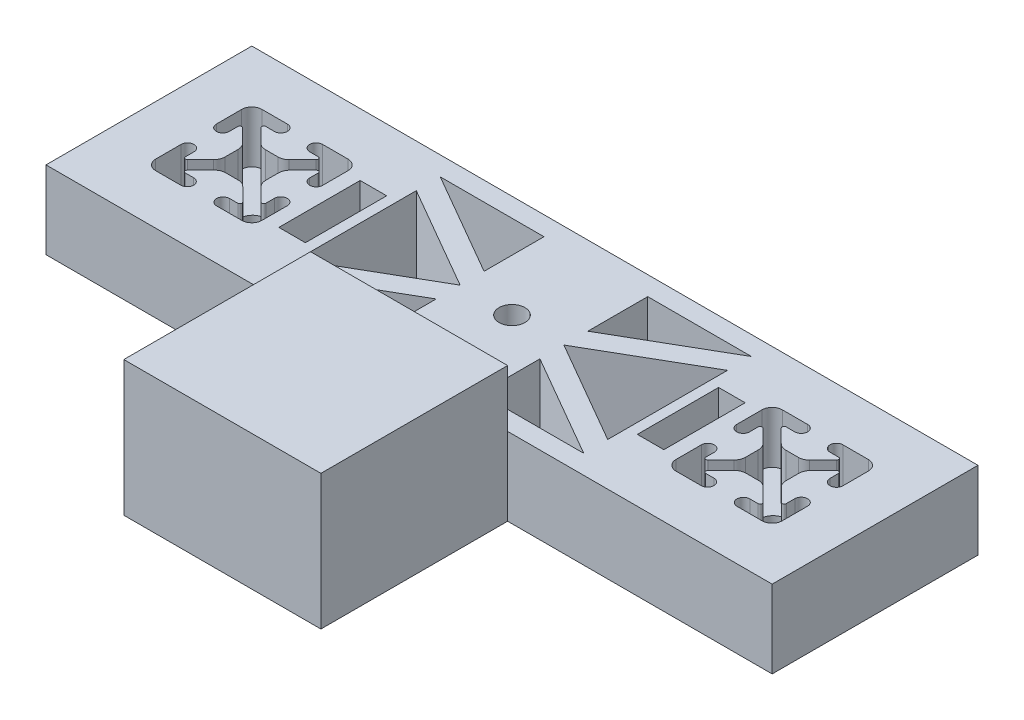
SolidWorks part; units mm, degrees
ref_plane "Front" through (0, 0, 0) normal (0, 0, 1) x (1, 0, 0)
ref_plane "Top" through (0, 0, 0) normal (0, 1, 0) x (1, 0, 0)
ref_plane "Right" through (0, 0, 0) normal (1, 0, 0) x (0, 0, -1)
sketch "Sketch1" plane through (0, 0, 0) normal (0, 1, 0) x (1, 0, 0)
  line L1 (0, 0) -> (177.8, 0)
  line L2 (0, 0) -> (0, 50.4)
  line L3 (0, 50.4) -> (177.8, 50.4)
  line L4 (177.8, 0) -> (177.8, 50.4)
  dimension "D1" = 177.8
  dimension "D2" = 50.4
extrude "Boss-Extrude1" add sketch "Sketch1" along normal blind 6.35
sketch "Sketch2" plane through (0, 6.35, 0) normal (0, 1, 0) x (1, 0, 0)
  line L0 (37.6996, 29.52) -> (37.6996, 35.7372) construction
  line L1 (35.7368, 37.7) -> (29.5196, 37.7) construction
  line L2 (29.5196, 35.56) -> (31.619, 35.56) construction
  line L3 (32.3326, 33.8353) -> (28.9966, 30.504) construction
  line L4 (26.7566, 29.5771) -> (23.643, 29.5771) construction
  line L5 (21.403, 30.504) -> (18.067, 33.8353) construction
  line L6 (18.7806, 35.56) -> (20.88, 35.56) construction
  line L7 (20.88, 37.7) -> (14.6628, 37.7) construction
  line L8 (12.7, 35.7372) -> (12.7, 29.52) construction
  line L9 (14.84, 29.52) -> (14.84, 31.5965) construction
  line L10 (16.5637, 32.3112) -> (19.7659, 29.1135) construction
  line L11 (20.743, 26.7568) -> (20.743, 23.6432) construction
  line L12 (19.7659, 21.2865) -> (16.5637, 18.0888) construction
  line L13 (14.84, 18.8035) -> (14.84, 20.88) construction
  line L14 (12.7, 20.88) -> (12.7, 14.6628) construction
  line L15 (14.6628, 12.7) -> (20.8121, 12.7) construction
  line L16 (20.8121, 14.84) -> (18.7806, 14.84) construction
  line L17 (18.067, 16.5647) -> (21.403, 19.896) construction
  line L18 (23.643, 20.8229) -> (26.7566, 20.8229) construction
  line L19 (28.9966, 19.896) -> (32.3326, 16.5647) construction
  line L20 (31.619, 14.84) -> (29.5875, 14.84) construction
  line L21 (29.5875, 12.7) -> (35.7368, 12.7) construction
  line L22 (37.6996, 14.6628) -> (37.6996, 20.88) construction
  line L23 (35.5596, 20.88) -> (35.5596, 18.8035) construction
  line L24 (33.8359, 18.0888) -> (30.6337, 21.2865) construction
  line L25 (29.6566, 23.6432) -> (29.6566, 26.7568) construction
  line L26 (30.6337, 29.1135) -> (33.8359, 32.3112) construction
  line L27 (35.5596, 31.5965) -> (35.5596, 29.52) construction
  line L28 (0, 50.4) -> (0, 0) construction
  line L29 (177.8, 50.4) -> (0, 50.4) construction
  line L30 (0, 0) -> (177.8, 0) construction
  line L31 (88.9, 50.4) -> (88.9, 0) construction
  line L32 (142.2404, 31.5965) -> (142.2404, 29.52) construction
  line L33 (147.1663, 29.1135) -> (143.9641, 32.3112) construction
  line L34 (148.1434, 23.6432) -> (148.1434, 26.7568) construction
  line L35 (143.9641, 18.0888) -> (147.1663, 21.2865) construction
  line L36 (142.2404, 20.88) -> (142.2404, 18.8035) construction
  line L37 (140.1004, 14.6628) -> (140.1004, 20.88) construction
  line L38 (148.2125, 12.7) -> (142.0632, 12.7) construction
  line L39 (146.181, 14.84) -> (148.2125, 14.84) construction
  line L40 (148.8034, 19.896) -> (145.4674, 16.5647) construction
  line L41 (154.157, 20.8229) -> (151.0434, 20.8229) construction
  line L42 (159.733, 16.5647) -> (156.397, 19.896) construction
  line L43 (156.9879, 14.84) -> (159.0194, 14.84) construction
  line L44 (163.1372, 12.7) -> (156.9879, 12.7) construction
  line L45 (165.1, 20.88) -> (165.1, 14.6628) construction
  line L46 (162.96, 18.8035) -> (162.96, 20.88) construction
  line L47 (158.0341, 21.2865) -> (161.2363, 18.0888) construction
  line L48 (157.057, 26.7568) -> (157.057, 23.6432) construction
  line L49 (161.2363, 32.3112) -> (158.0341, 29.1135) construction
  line L50 (162.96, 29.52) -> (162.96, 31.5965) construction
  line L51 (165.1, 35.7372) -> (165.1, 29.52) construction
  line L52 (156.92, 37.7) -> (163.1372, 37.7) construction
  line L53 (159.0194, 35.56) -> (156.92, 35.56) construction
  line L54 (156.397, 30.504) -> (159.733, 33.8353) construction
  line L55 (151.0434, 29.5771) -> (154.157, 29.5771) construction
  line L56 (145.4674, 33.8353) -> (148.8034, 30.504) construction
  line L57 (148.2804, 35.56) -> (146.181, 35.56) construction
  line L58 (142.0632, 37.7) -> (148.2804, 37.7) construction
  line L59 (140.1004, 29.52) -> (140.1004, 35.7372) construction
  line L60 (38.2076, 29.52) -> (38.2076, 35.7372)
  line L62 (0, 50.4) -> (0, 0)
  line L63 (0, 0) -> (177.8, 0)
  line L64 (177.8, 50.4) -> (177.8, 0)
  line L65 (35.7368, 38.208) -> (29.5196, 38.208)
  line L66 (29.5196, 35.052) -> (31.619, 35.052)
  line L67 (31.9737, 34.1948) -> (28.6376, 30.8635)
  line L68 (26.7566, 30.0851) -> (23.643, 30.0851)
  line L69 (21.762, 30.8635) -> (18.4259, 34.1948)
  line L70 (18.7806, 35.052) -> (20.88, 35.052)
  line L71 (20.88, 38.208) -> (14.6628, 38.208)
  line L72 (12.192, 35.7372) -> (12.192, 29.52)
  line L73 (15.348, 29.52) -> (15.348, 31.5965)
  line L74 (16.2047, 31.9517) -> (19.4069, 28.7541)
  line L75 (20.235, 26.7568) -> (20.235, 23.6432)
  line L76 (19.4069, 21.6459) -> (16.2047, 18.4483)
  line L77 (15.348, 18.8035) -> (15.348, 20.88)
  line L78 (12.192, 20.88) -> (12.192, 14.6628)
  line L79 (14.6628, 12.192) -> (20.8121, 12.192)
  line L80 (20.8121, 15.348) -> (18.7806, 15.348)
  line L81 (18.4259, 16.2052) -> (21.762, 19.5365)
  line L82 (23.643, 20.3149) -> (26.7566, 20.3149)
  line L83 (28.6376, 19.5365) -> (31.9737, 16.2052)
  line L84 (31.619, 15.348) -> (29.5875, 15.348)
  line L85 (29.5875, 12.192) -> (35.7368, 12.192)
  line L86 (38.2076, 14.6628) -> (38.2076, 20.88)
  line L87 (35.0516, 20.88) -> (35.0516, 18.8035)
  line L88 (34.1949, 18.4483) -> (30.9927, 21.6459)
  line L89 (30.1646, 23.6432) -> (30.1646, 26.7568)
  line L90 (30.9927, 28.7541) -> (34.1949, 31.9517)
  line L91 (35.0516, 31.5965) -> (35.0516, 29.52)
  line L92 (142.7484, 31.5965) -> (142.7484, 29.52)
  line L93 (139.5924, 29.52) -> (139.5924, 35.7372)
  line L94 (142.0632, 38.208) -> (148.2804, 38.208)
  line L95 (148.2804, 35.052) -> (146.181, 35.052)
  line L96 (145.8263, 34.1948) -> (149.1624, 30.8635)
  line L97 (151.0434, 30.0851) -> (154.157, 30.0851)
  line L98 (156.038, 30.8635) -> (159.3741, 34.1948)
  line L99 (159.0194, 35.052) -> (156.92, 35.052)
  line L100 (156.92, 38.208) -> (163.1372, 38.208)
  line L101 (165.608, 35.7372) -> (165.608, 29.52)
  line L102 (162.452, 29.52) -> (162.452, 31.5965)
  line L103 (161.5953, 31.9517) -> (158.3931, 28.7541)
  line L104 (157.565, 26.7568) -> (157.565, 23.6432)
  line L105 (158.3931, 21.6459) -> (161.5953, 18.4483)
  line L106 (162.452, 18.8035) -> (162.452, 20.88)
  line L107 (165.608, 20.88) -> (165.608, 14.6628)
  line L108 (163.1372, 12.192) -> (156.9879, 12.192)
  line L109 (156.9879, 15.348) -> (159.0194, 15.348)
  line L110 (159.3741, 16.2052) -> (156.038, 19.5365)
  line L111 (154.157, 20.3149) -> (151.0434, 20.3149)
  line L112 (149.1624, 19.5365) -> (145.8263, 16.2052)
  line L113 (146.181, 15.348) -> (148.2125, 15.348)
  line L114 (148.2125, 12.192) -> (142.0632, 12.192)
  line L115 (139.5924, 14.6628) -> (139.5924, 20.88)
  line L116 (142.7484, 20.88) -> (142.7484, 18.8035)
  line L117 (143.6051, 18.4483) -> (146.8073, 21.6459)
  line L118 (147.6354, 23.6432) -> (147.6354, 26.7568)
  line L119 (146.8073, 28.7541) -> (143.6051, 31.9517)
  line L120 (177.8, 50.4) -> (0, 50.4)
  arc A1 (37.6996, 35.7372) -> (35.7368, 37.7) centre (35.7368, 35.7372) ccw construction
  arc A2 (29.5196, 37.7) -> (29.5196, 35.56) centre (29.5196, 36.63) ccw construction
  arc A3 (31.619, 35.56) -> (32.3326, 33.8353) centre (31.619, 34.55) cw construction
  arc A4 (28.9966, 30.504) -> (26.7566, 29.5771) centre (26.7566, 32.7471) cw construction
  arc A5 (23.643, 29.5771) -> (21.403, 30.504) centre (23.643, 32.7471) cw construction
  arc A6 (18.067, 33.8353) -> (18.7806, 35.56) centre (18.7806, 34.55) cw construction
  arc A7 (20.88, 35.56) -> (20.88, 37.7) centre (20.88, 36.63) ccw construction
  arc A8 (14.6628, 37.7) -> (12.7, 35.7372) centre (14.6628, 35.7372) ccw construction
  arc A9 (12.7, 29.52) -> (14.84, 29.52) centre (13.77, 29.52) ccw construction
  arc A10 (14.84, 31.5965) -> (16.5637, 32.3112) centre (15.85, 31.5965) cw construction
  arc A11 (19.7659, 29.1135) -> (20.743, 26.7568) centre (17.4126, 26.7568) cw construction
  arc A12 (20.743, 23.6432) -> (19.7659, 21.2865) centre (17.4126, 23.6432) cw construction
  arc A13 (16.5637, 18.0888) -> (14.84, 18.8035) centre (15.85, 18.8035) cw construction
  arc A14 (14.84, 20.88) -> (12.7, 20.88) centre (13.77, 20.88) ccw construction
  arc A15 (12.7, 14.6628) -> (14.6628, 12.7) centre (14.6628, 14.6628) ccw construction
  arc A16 (20.8121, 12.7) -> (20.8121, 14.84) centre (20.8121, 13.77) ccw construction
  arc A17 (18.7806, 14.84) -> (18.067, 16.5647) centre (18.7806, 15.85) cw construction
  arc A18 (21.403, 19.896) -> (23.643, 20.8229) centre (23.643, 17.6529) cw construction
  arc A19 (26.7566, 20.8229) -> (28.9966, 19.896) centre (26.7566, 17.6529) cw construction
  arc A20 (32.3326, 16.5647) -> (31.619, 14.84) centre (31.619, 15.85) cw construction
  arc A21 (29.5875, 14.84) -> (29.5875, 12.7) centre (29.5875, 13.77) ccw construction
  arc A22 (35.7368, 12.7) -> (37.6996, 14.6628) centre (35.7368, 14.6628) ccw construction
  arc A23 (37.6996, 20.88) -> (35.5596, 20.88) centre (36.6296, 20.88) ccw construction
  arc A24 (35.5596, 18.8035) -> (33.8359, 18.0888) centre (34.5496, 18.8035) cw construction
  arc A25 (30.6337, 21.2865) -> (29.6566, 23.6432) centre (32.987, 23.6432) cw construction
  arc A26 (29.6566, 26.7568) -> (30.6337, 29.1135) centre (32.987, 26.7568) cw construction
  arc A27 (33.8359, 32.3112) -> (35.5596, 31.5965) centre (34.5496, 31.5965) cw construction
  arc A28 (35.5596, 29.52) -> (37.6996, 29.52) centre (36.6296, 29.52) ccw construction
  arc A29 (142.2404, 29.52) -> (140.1004, 29.52) centre (141.1704, 29.52) cw construction
  arc A30 (143.9641, 32.3112) -> (142.2404, 31.5965) centre (143.2504, 31.5965) ccw construction
  arc A31 (148.1434, 26.7568) -> (147.1663, 29.1135) centre (144.813, 26.7568) ccw construction
  arc A32 (147.1663, 21.2865) -> (148.1434, 23.6432) centre (144.813, 23.6432) ccw construction
  arc A33 (142.2404, 18.8035) -> (143.9641, 18.0888) centre (143.2504, 18.8035) ccw construction
  arc A34 (140.1004, 20.88) -> (142.2404, 20.88) centre (141.1704, 20.88) cw construction
  arc A35 (142.0632, 12.7) -> (140.1004, 14.6628) centre (142.0632, 14.6628) cw construction
  arc A36 (148.2125, 14.84) -> (148.2125, 12.7) centre (148.2125, 13.77) cw construction
  arc A37 (145.4674, 16.5647) -> (146.181, 14.84) centre (146.181, 15.85) ccw construction
  arc A38 (151.0434, 20.8229) -> (148.8034, 19.896) centre (151.0434, 17.6529) ccw construction
  arc A39 (156.397, 19.896) -> (154.157, 20.8229) centre (154.157, 17.6529) ccw construction
  arc A40 (159.0194, 14.84) -> (159.733, 16.5647) centre (159.0194, 15.85) ccw construction
  arc A41 (156.9879, 12.7) -> (156.9879, 14.84) centre (156.9879, 13.77) cw construction
  arc A42 (165.1, 14.6628) -> (163.1372, 12.7) centre (163.1372, 14.6628) cw construction
  arc A43 (162.96, 20.88) -> (165.1, 20.88) centre (164.03, 20.88) cw construction
  arc A44 (161.2363, 18.0888) -> (162.96, 18.8035) centre (161.95, 18.8035) ccw construction
  arc A45 (157.057, 23.6432) -> (158.0341, 21.2865) centre (160.3874, 23.6432) ccw construction
  arc A46 (158.0341, 29.1135) -> (157.057, 26.7568) centre (160.3874, 26.7568) ccw construction
  arc A47 (162.96, 31.5965) -> (161.2363, 32.3112) centre (161.95, 31.5965) ccw construction
  arc A48 (165.1, 29.52) -> (162.96, 29.52) centre (164.03, 29.52) cw construction
  arc A49 (163.1372, 37.7) -> (165.1, 35.7372) centre (163.1372, 35.7372) cw construction
  arc A50 (156.92, 35.56) -> (156.92, 37.7) centre (156.92, 36.63) cw construction
  arc A51 (159.733, 33.8353) -> (159.0194, 35.56) centre (159.0194, 34.55) ccw construction
  arc A52 (154.157, 29.5771) -> (156.397, 30.504) centre (154.157, 32.7471) ccw construction
  arc A53 (148.8034, 30.504) -> (151.0434, 29.5771) centre (151.0434, 32.7471) ccw construction
  arc A54 (146.181, 35.56) -> (145.4674, 33.8353) centre (146.181, 34.55) ccw construction
  arc A55 (148.2804, 37.7) -> (148.2804, 35.56) centre (148.2804, 36.63) cw construction
  arc A56 (140.1004, 35.7372) -> (142.0632, 37.7) centre (142.0632, 35.7372) cw construction
  arc A58 (38.2076, 35.7372) -> (35.7368, 38.208) centre (35.7368, 35.7372) ccw
  arc A59 (29.5196, 38.208) -> (29.5196, 35.052) centre (29.5196, 36.63) ccw
  arc A60 (31.619, 35.052) -> (31.9737, 34.1948) centre (31.619, 34.55) cw
  arc A61 (28.6376, 30.8635) -> (26.7566, 30.0851) centre (26.7566, 32.7471) cw
  arc A62 (23.643, 30.0851) -> (21.762, 30.8635) centre (23.643, 32.7471) cw
  arc A63 (18.4259, 34.1948) -> (18.7806, 35.052) centre (18.7806, 34.55) cw
  arc A64 (20.88, 35.052) -> (20.88, 38.208) centre (20.88, 36.63) ccw
  arc A65 (14.6628, 38.208) -> (12.192, 35.7372) centre (14.6628, 35.7372) ccw
  arc A66 (12.192, 29.52) -> (15.348, 29.52) centre (13.77, 29.52) ccw
  arc A67 (15.348, 31.5965) -> (16.2047, 31.9517) centre (15.85, 31.5965) cw
  arc A68 (19.4069, 28.7541) -> (20.235, 26.7568) centre (17.4126, 26.7568) cw
  arc A69 (20.235, 23.6432) -> (19.4069, 21.6459) centre (17.4126, 23.6432) cw
  arc A70 (16.2047, 18.4483) -> (15.348, 18.8035) centre (15.85, 18.8035) cw
  arc A71 (15.348, 20.88) -> (12.192, 20.88) centre (13.77, 20.88) ccw
  arc A72 (12.192, 14.6628) -> (14.6628, 12.192) centre (14.6628, 14.6628) ccw
  arc A73 (20.8121, 12.192) -> (20.8121, 15.348) centre (20.8121, 13.77) ccw
  arc A74 (18.7806, 15.348) -> (18.4259, 16.2052) centre (18.7806, 15.85) cw
  arc A75 (21.762, 19.5365) -> (23.643, 20.3149) centre (23.643, 17.6529) cw
  arc A76 (26.7566, 20.3149) -> (28.6376, 19.5365) centre (26.7566, 17.6529) cw
  arc A77 (31.9737, 16.2052) -> (31.619, 15.348) centre (31.619, 15.85) cw
  arc A78 (29.5875, 15.348) -> (29.5875, 12.192) centre (29.5875, 13.77) ccw
  arc A79 (35.7368, 12.192) -> (38.2076, 14.6628) centre (35.7368, 14.6628) ccw
  arc A80 (38.2076, 20.88) -> (35.0516, 20.88) centre (36.6296, 20.88) ccw
  arc A81 (35.0516, 18.8035) -> (34.1949, 18.4483) centre (34.5496, 18.8035) cw
  arc A82 (30.9927, 21.6459) -> (30.1646, 23.6432) centre (32.987, 23.6432) cw
  arc A83 (30.1646, 26.7568) -> (30.9927, 28.7541) centre (32.987, 26.7568) cw
  arc A84 (34.1949, 31.9517) -> (35.0516, 31.5965) centre (34.5496, 31.5965) cw
  arc A85 (35.0516, 29.52) -> (38.2076, 29.52) centre (36.6296, 29.52) ccw
  arc A86 (142.7484, 29.52) -> (139.5924, 29.52) centre (141.1704, 29.52) cw
  arc A87 (139.5924, 35.7372) -> (142.0632, 38.208) centre (142.0632, 35.7372) cw
  arc A88 (148.2804, 38.208) -> (148.2804, 35.052) centre (148.2804, 36.63) cw
  arc A89 (146.181, 35.052) -> (145.8263, 34.1948) centre (146.181, 34.55) ccw
  arc A90 (149.1624, 30.8635) -> (151.0434, 30.0851) centre (151.0434, 32.7471) ccw
  arc A91 (154.157, 30.0851) -> (156.038, 30.8635) centre (154.157, 32.7471) ccw
  arc A92 (159.3741, 34.1948) -> (159.0194, 35.052) centre (159.0194, 34.55) ccw
  arc A93 (156.92, 35.052) -> (156.92, 38.208) centre (156.92, 36.63) cw
  arc A94 (163.1372, 38.208) -> (165.608, 35.7372) centre (163.1372, 35.7372) cw
  arc A95 (165.608, 29.52) -> (162.452, 29.52) centre (164.03, 29.52) cw
  arc A96 (162.452, 31.5965) -> (161.5953, 31.9517) centre (161.95, 31.5965) ccw
  arc A97 (158.3931, 28.7541) -> (157.565, 26.7568) centre (160.3874, 26.7568) ccw
  arc A98 (157.565, 23.6432) -> (158.3931, 21.6459) centre (160.3874, 23.6432) ccw
  arc A99 (161.5953, 18.4483) -> (162.452, 18.8035) centre (161.95, 18.8035) ccw
  arc A100 (162.452, 20.88) -> (165.608, 20.88) centre (164.03, 20.88) cw
  arc A101 (165.608, 14.6628) -> (163.1372, 12.192) centre (163.1372, 14.6628) cw
  arc A102 (156.9879, 12.192) -> (156.9879, 15.348) centre (156.9879, 13.77) cw
  arc A103 (159.0194, 15.348) -> (159.3741, 16.2052) centre (159.0194, 15.85) ccw
  arc A104 (156.038, 19.5365) -> (154.157, 20.3149) centre (154.157, 17.6529) ccw
  arc A105 (151.0434, 20.3149) -> (149.1624, 19.5365) centre (151.0434, 17.6529) ccw
  arc A106 (145.8263, 16.2052) -> (146.181, 15.348) centre (146.181, 15.85) ccw
  arc A107 (148.2125, 15.348) -> (148.2125, 12.192) centre (148.2125, 13.77) cw
  arc A108 (142.0632, 12.192) -> (139.5924, 14.6628) centre (142.0632, 14.6628) cw
  arc A109 (139.5924, 20.88) -> (142.7484, 20.88) centre (141.1704, 20.88) cw
  arc A110 (142.7484, 18.8035) -> (143.6051, 18.4483) centre (143.2504, 18.8035) ccw
  arc A111 (146.8073, 21.6459) -> (147.6354, 23.6432) centre (144.813, 23.6432) ccw
  arc A112 (147.6354, 26.7568) -> (146.8073, 28.7541) centre (144.813, 26.7568) ccw
  arc A113 (143.6051, 31.9517) -> (142.7484, 31.5965) centre (143.2504, 31.5965) ccw
  dimension "D2" = 1.07
  dimension "D3" = 3.17
  dimension "D4" = 3.3305
  dimension "D8" = 1.9628
  dimension "D9" = 1.01
  dimension "D5" = 12.7
  dimension "D6" = 12.7
  dimension "D7" = 12.7
  dimension "D10" = 16.5637
  dimension "D12" = 0.508
  dimension "D13" = 0.508
extrude "Boss-Extrude2" add sketch "Sketch2" along normal blind 12.7
sketch "Sketch3" plane through (0, 19.05, 0) normal (0, 1, 0) x (1, 0, 0)
  line L0 (177.8, 50.4) -> (0, 50.4) construction
  line L1 (0, 50.4) -> (0, 0) construction
  circle A0 centre (88.9, 25.2) radius 3.175
  point P4 (88.9, 50.4)
  point P7 (0, 25.2)
  dimension "D1" = 6.35
extrude "Cut-Extrude1" cut sketch "Sketch3" against normal blind 10.16
sketch "Sketch4" plane through (0, 19.05, 0) normal (0, 1, 0) x (1, 0, 0)
  line L0 (50.8, 45.7306) -> (76.2, 45.7306)
  line L1 (76.2, 45.7306) -> (76.2, 31.0659)
  line L2 (76.2, 31.0659) -> (50.8, 45.7306)
  line L3 (76.2, 19.3341) -> (76.2, 4.6694)
  line L4 (76.2, 4.6694) -> (50.8, 4.6694)
  line L5 (50.8, 4.6694) -> (76.2, 19.3341)
  line L6 (50.8, 39.8647) -> (50.8, 10.5353)
  line L7 (50.8, 10.5353) -> (76.2, 25.2)
  line L8 (76.2, 25.2) -> (50.8, 39.8647)
  line L9 (0, 50.4) -> (0, 0) construction
  line L10 (88.9, 50.4) -> (88.9, 0) construction
  line L11 (177.8, 50.4) -> (0, 50.4) construction
  line L12 (0, 0) -> (177.8, 0) construction
  line L13 (101.6, 25.2) -> (127, 39.8647)
  line L14 (127, 10.5353) -> (101.6, 25.2)
  line L15 (127, 39.8647) -> (127, 10.5353)
  line L16 (127, 4.6694) -> (101.6, 19.3341)
  line L17 (101.6, 4.6694) -> (127, 4.6694)
  line L18 (101.6, 19.3341) -> (101.6, 4.6694)
  line L19 (101.6, 31.0659) -> (127, 45.7306)
  line L20 (101.6, 45.7306) -> (101.6, 31.0659)
  line L21 (127, 45.7306) -> (101.6, 45.7306)
  point P18 (88.9, 25.2)
  dimension "D1" = 25.4
  dimension "D2" = 25.4
  dimension "D3" = 50.8
  dimension "D4" = 5.08
  dimension "D5" = 5.08
  dimension "D7" = 60
extrude "Cut-Extrude2" cut sketch "Sketch4" against normal through all
sketch "Sketch5" plane through (0, 19.05, 0) normal (0, 1, 0) x (1, 0, 0)
  line L0 (0, 50.4) -> (0, 0) construction
  line L1 (41.7636, 35.15) -> (48.2636, 35.15)
  line L2 (41.7636, 35.15) -> (41.7636, 15.25)
  line L3 (41.7636, 15.25) -> (48.2636, 15.25)
  line L4 (48.2636, 35.15) -> (48.2636, 15.25)
  line L5 (38.2076, 29.52) -> (38.2076, 35.7372) construction
  point P6 (0, 25.2)
  point P7 (48.2636, 25.2)
  dimension "D1" = 6.5
  dimension "D2" = 19.9
  dimension "D3" = 3.556
extrude "Cut-Extrude3" cut sketch "Sketch5" against normal blind 10.2
sketch "Sketch6" plane through (0, 8.85, 0) normal (0, 1, 0) x (1, 0, 0)
  line L0 (48.2636, 15.25) -> (48.2636, 35.15) construction
  line L1 (41.7636, 35.15) -> (48.2636, 35.15)
  line L2 (41.7636, 35.15) -> (41.7636, 30.578)
  line L3 (41.7636, 30.578) -> (48.2636, 30.578)
  line L4 (48.2636, 35.15) -> (48.2636, 30.578)
  line L5 (41.7636, 35.15) -> (41.7636, 15.25) construction
  line L6 (48.2636, 15.25) -> (48.2636, 35.15) construction
  line L7 (41.7636, 27.486) -> (48.2636, 27.486)
  line L8 (41.7636, 27.486) -> (41.7636, 22.914)
  line L9 (41.7636, 22.914) -> (48.2636, 22.914)
  line L10 (48.2636, 27.486) -> (48.2636, 22.914)
  line L12 (41.7636, 15.25) -> (48.2636, 15.25)
  line L13 (41.7636, 15.25) -> (41.7636, 19.822)
  line L14 (41.7636, 19.822) -> (48.2636, 19.822)
  line L15 (48.2636, 15.25) -> (48.2636, 19.822)
  line L16 (41.7636, 25.2) -> (0, 25.2) construction
  line L17 (0, 50.4) -> (0, 0) construction
  dimension "D1" = 4.572
extrude "Cut-Extrude4" cut sketch "Sketch6" against normal through all
ref_plane "Plane1" through (88.9, 0, 0) normal (-1, 0, 0) x (0, 0, 1)
mirror "Mirror1" about plane through (88.9, 0, 0) normal (-1, 0, 0) of "Cut-Extrude4", "Cut-Extrude3"
sketch "Sketch7" plane through (0, 6.35, 0) normal (0, 1, 0) x (1, 0, 0)
  line L0 (26.7566, 30.0851) -> (23.643, 30.0851) construction
  line L1 (30.1646, 23.6432) -> (30.1646, 26.7568) construction
  circle A0 centre (25.3386, 25.2591) radius 2.921
  dimension "D1" = 5.842
  dimension "D2" = 4.826
  dimension "D3" = 4.826
extrude "Cut-Extrude5" cut sketch "Sketch7" against normal through all both and the other way through all
sketch "Sketch8" plane through (0, 6.35, 0) normal (0, 1, 0) x (1, 0, 0)
  line L0 (154.157, 30.0851) -> (151.0434, 30.0851) construction
  line L1 (157.565, 23.6432) -> (157.565, 26.7568) construction
  circle A0 centre (152.739, 25.2591) radius 2.921
  dimension "D1" = 5.842
  dimension "D2" = 4.826
  dimension "D3" = 4.826
extrude "Cut-Extrude6" cut sketch "Sketch8" against normal through all both and the other way through all
chamfer "Chamfer2" distance 3.302 angle 45 1 edges at (152.739, 0, -22.3381)
chamfer "Chamfer3" distance 3.302 angle 45 1 edges at (25.3386, 0, -22.3381)
sketch "Sketch9" plane through (0, 0, 0) normal (0, 1, 0) x (1, 0, 0)
  line L0 (113.03, 0) -> (113.03, -45.72)
  line L1 (85.725, 25.2) -> (92.075, 25.2) construction
  line L3 (0, 0) -> (177.8, 0) construction
  line L6 (64.77, 0) -> (113.03, 0)
  line L8 (64.77, -45.72) -> (113.03, -45.72)
  line L13 (64.77, 0) -> (64.77, -45.72)
  circle A1 centre (88.9, 25.2) radius 3.175 construction
  point P0 (88.9, 0)
  point P1 (88.9, -45.72)
  point P2 (88.9, 25.2)
  dimension "D1" = 45.72
  dimension "D2" = 48.26
sketch "Sketch11" plane through (0, 0, 0) normal (0, 1, 0) x (1, 0, 0)
  line L0 (0, 0) -> (177.8, 0) construction
  line L2 (41.7636, 15.25) -> (41.7636, 0)
  line L3 (41.7636, 0) -> (48.2636, 0)
  line L4 (48.2636, 15.25) -> (48.2636, 0)
  line L5 (48.2636, 15.25) -> (48.2636, 35.15) construction
  line L6 (177.8, 50.4) -> (0, 50.4) construction
  line L8 (41.7636, 35.15) -> (41.7636, 50.4)
  line L9 (41.7636, 50.4) -> (48.2636, 50.4)
  line L10 (48.2636, 35.15) -> (48.2636, 50.4)
  line L11 (41.7636, 35.15) -> (41.7636, 15.25)
  line L12 (48.2636, 35.15) -> (48.2636, 15.25)
extrude "Cut-Extrude8" cut sketch "Sketch11" along normal blind 5.08
extrude "Boss-Extrude4" add sketch "Sketch9" along normal blind 33.02
